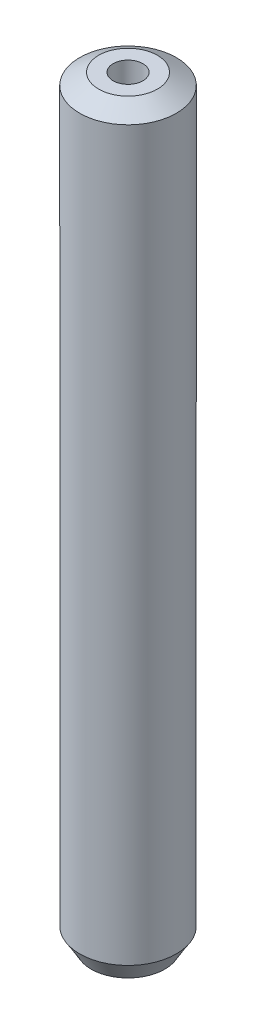
SolidWorks part; units mm, degrees
ref_plane "Front Plane" through (0, 0, 0) normal (0, 0, 1) x (1, 0, 0)
ref_plane "Top Plane" through (0, 0, 0) normal (0, 1, 0) x (1, 0, 0)
ref_plane "Right Plane" through (0, 0, 0) normal (1, 0, 0) x (0, 0, -1)
sketch "Sketch1" plane through (0, 0, 0) normal (0, 1, 0) x (1, 0, 0)
  circle A0 centre (0, 0) radius 10
  dimension "SHAFT_OD" = 20
extrude "Boss-Extrude1" add sketch "Sketch1" along normal blind 157.0069
sketch "Sketch2" plane through (0, 0, 0) normal (0, 1, 0) x (1, 0, 0)
  circle A0 centre (0, 0) radius 3.082
  dimension "BORE_D" = 6.164
extrude "Cut-Extrude1" cut sketch "Sketch2" along normal through all
chamfer "Chamfer1" distance 2.3639 angle 58.943 2 edges at (0, 157.0069, 10) (0, 0, 10) first distance on face at (0, 157.0069, 10) first distance on face at (0, 0, 3.082)
